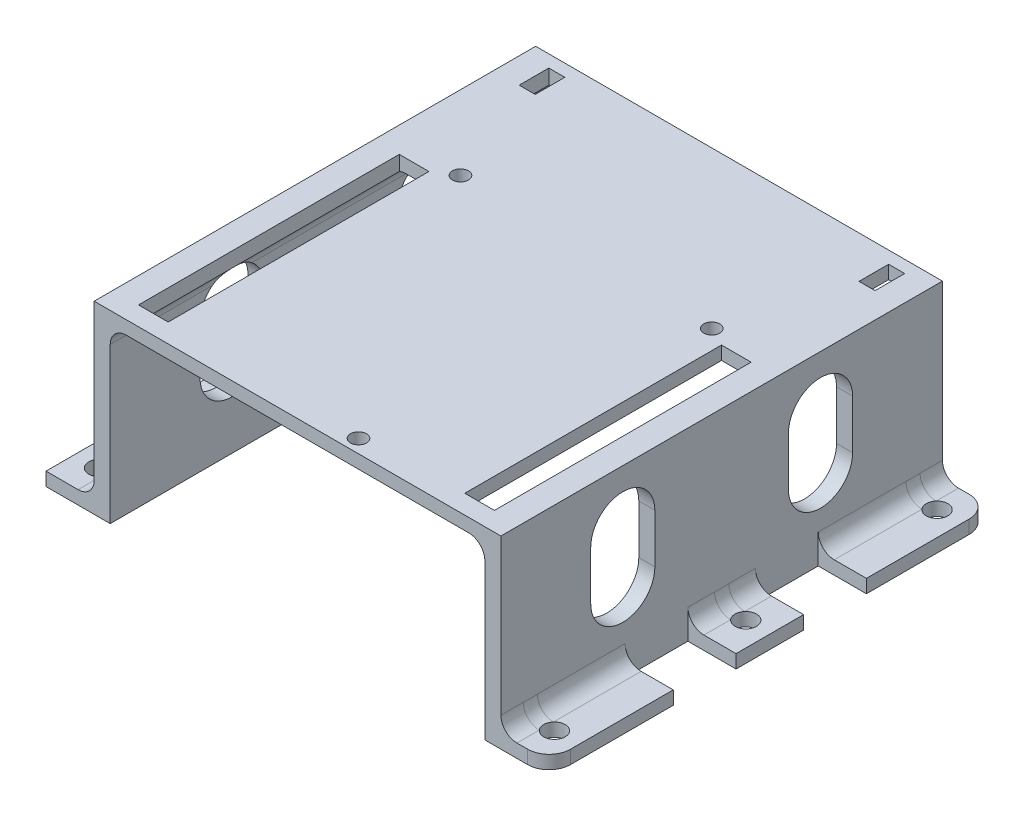
SolidWorks part; units mm, degrees
ref_plane "Front Plane" through (0, 0, 0) normal (0, 0, 1) x (1, 0, 0)
ref_plane "Top Plane" through (0, 0, 0) normal (0, 1, 0) x (1, 0, 0)
ref_plane "Right Plane" through (0, 0, 0) normal (1, 0, 0) x (0, 0, -1)
sketch "Sketch1" plane through (0, 0, 0) normal (0, 1, 0) x (1, 0, 0)
  line L0 (-35, 41.25) -> (-38, 41.25)
  line L1 (-35, -41.25) -> (35, -41.25)
  line L2 (-35, -41.25) -> (-35, 41.25)
  line L3 (-35, 41.25) -> (35, 41.25)
  line L4 (35, -41.25) -> (35, 41.25)
  line L5 (-35, -41.25) -> (35, 41.25) construction
  line L6 (-35, 41.25) -> (35, -41.25) construction
  line L7 (-38, 41.25) -> (-38, -41.25)
  line L8 (-38, -41.25) -> (-35, -41.25)
  line L9 (-38, -41.25) -> (-47, -41.25)
  line L10 (-47, -41.25) -> (-47, 41.25)
  line L11 (-47, 41.25) -> (-38, 41.25)
  line L12 (0, 21.0903) -> (0, -28.1695) construction
  line L13 (47, 41.25) -> (38, 41.25)
  line L14 (47, -41.25) -> (47, 41.25)
  line L15 (38, -41.25) -> (47, -41.25)
  line L16 (38, 41.25) -> (38, -41.25)
  line L17 (38, -41.25) -> (35, -41.25)
  line L18 (35, 41.25) -> (38, 41.25)
  line L19 (-42.5, 41.25) -> (-42.5, -41.25) construction
  line L20 (42.5, 41.25) -> (42.5, -41.25) construction
  line L21 (-58.5063, 0) -> (72.588, 0) construction
  circle A0 centre (-42.5, 35.75) radius 2
  circle A1 centre (-42.5, -35.75) radius 2
  circle A2 centre (42.5, -35.75) radius 2
  circle A3 centre (42.5, 35.75) radius 2
  circle A4 centre (-42.5, 0) radius 2
  circle A5 centre (42.5, 0) radius 2
  point P0 (0, 0)
  dimension "D3" = 4
  dimension "D4" = 4
  dimension "D5" = 5.5
  dimension "D9" = 4
  dimension "D10" = 4
  dimension "D1" = 3
  dimension "D2" = 9
  dimension "D6" = 5.5
  dimension "D7" = 82.5
  dimension "D8" = 70
extrude "Boss-Extrude1" add sketch "Sketch1" along normal blind 2.5 contours L11 L10 L9 L7 A1 A0 | L13 L16 L15 L14 A2 A3 region at (-38.8299, 0, 0) region at (42.5, 0, -40.4201)
extrude "Boss-Extrude2" add sketch "Sketch1<3>" along normal blind 32 contours L7 L8 L2 L0 | L18 L4 L17 L16 region at (-36.5, 0, 0) region at (36.5, 0, 0)
sketch "Sketch1<3>" plane through (0, 0, 0) normal (0, 1, 0) x (1, 0, 0) same geometry as "Sketch1"
extrude "Boss-Extrude3" add sketch "Sketch1<5>" along normal blind 2.5 from surface contours L7 L8 L2 L0 | L18 L4 L17 L16 | L1 L4 L3 L2 region at (-36.5, 0, 0) region at (0, 0, 0) region at (36.5, 0, 0) starting at face at (-36.5, 32, 0)
sketch "Sketch1<5>" plane through (0, 0, 0) normal (0, 1, 0) x (1, 0, 0) same geometry as "Sketch1"
fillet "Fillet1" radius 3 2 edges at (35, 32, 0) (-35, 32, 0)
fillet "Fillet2" radius 4 2 edges at (47, 1.25, 41.25) (47, 1.25, -41.25)
sketch "Sketch2" plane through (0, 2.5, 0) normal (0, 1, 0) x (1, 0, 0)
  line L0 (-42.5, 0) -> (42.5, 0) construction
  line L1 (48.0101, 18.0465) -> (38, 18.0465)
  line L2 (38, -41.25) -> (38, 41.25) construction
  line L3 (38, 18.0465) -> (38, 6.3106)
  line L4 (38, 6.3106) -> (48.0101, 6.3106)
  line L5 (48.0101, 6.3106) -> (48.0101, 18.0465)
  line L6 (48.0101, -6.3106) -> (48.0101, -18.0465)
  line L7 (38, -6.3106) -> (48.0101, -6.3106)
  line L8 (38, -18.0465) -> (38, -6.3106)
  line L9 (48.0101, -18.0465) -> (38, -18.0465)
extrude "Cut-Extrude1" cut sketch "Sketch2" against normal through all both and the other way through all
fillet "Fillet4" radius 3 4 edges at (-38, 2.5, 0) (38, 2.5, 29.6482) (38, 2.5, 0) (38, 2.5, -29.6482)
sketch "Sketch3" plane through (-38, 0, 0) normal (-1, 0, 0) x (0, 0, 1)
  line L0 (18.4733, 15.128) -> (18.4733, 24.2824) construction
  line L1 (12.4833, 15.128) -> (12.4833, 24.2824)
  line L2 (24.4633, 15.128) -> (24.4633, 24.2824)
  line L3 (0, 7.6501) -> (0, 29.8023) construction
  line L4 (-18.4733, 15.128) -> (-18.4733, 24.2824) construction
  line L5 (-12.4833, 15.128) -> (-12.4833, 24.2824)
  line L6 (-24.4633, 15.128) -> (-24.4633, 24.2824)
  arc A0 (12.4833, 15.128) -> (24.4633, 15.128) centre (18.4733, 15.128) ccw
  arc A1 (24.4633, 24.2824) -> (12.4833, 24.2824) centre (18.4733, 24.2824) ccw
  arc A2 (-12.4833, 15.128) -> (-24.4633, 15.128) centre (-18.4733, 15.128) cw
  arc A3 (-24.4633, 24.2824) -> (-12.4833, 24.2824) centre (-18.4733, 24.2824) cw
  point P2 (18.4733, 19.7052)
  point P12 (-18.4733, 19.7052)
extrude "Cut-Extrude2" cut sketch "Sketch3" against normal through all both and the other way through all
sketch "Sketch4" plane through (0, 34.5, 0) normal (0, 1, 0) x (1, 0, 0)
  line L0 (-38, -41.25) -> (-38, 41.25) construction
  line L1 (38, -41.25) -> (-38, -41.25) construction
  line L2 (-31.75, -36.21) -> (-29.21, -36.21) construction
  line L3 (-31.75, -36.21) -> (-31.75, 9.51) construction
  line L4 (-31.75, 9.51) -> (-29.21, 9.51) construction
  line L5 (-29.21, -36.21) -> (-29.21, 9.51) construction
  line L6 (29.21, -36.21) -> (31.75, -36.21) construction
  line L7 (29.21, -36.21) -> (29.21, 9.51) construction
  line L8 (29.21, 9.51) -> (31.75, 9.51) construction
  line L9 (31.75, -36.21) -> (31.75, 9.51) construction
  line L10 (-31.75, 34.91) -> (-31.75, 37.45) construction
  line L11 (-33.25, -37.71) -> (-27.71, -37.71)
  line L12 (-33.25, -37.71) -> (-33.25, 11.01)
  line L13 (-33.25, 11.01) -> (-27.71, 11.01)
  line L14 (-27.71, -37.71) -> (-27.71, 11.01)
  line L15 (27.71, -37.71) -> (33.25, -37.71)
  line L16 (27.71, -37.71) -> (27.71, 10.26)
  line L17 (27.71, 10.26) -> (33.25, 10.26)
  line L18 (33.25, -37.71) -> (33.25, 10.26)
  line L19 (31.75, 34.91) -> (31.75, 37.45) construction
  line L21 (-31.75, 37.45) -> (31.75, 37.45) construction
  line L23 (-33.25, 33.41) -> (-30.25, 33.41)
  line L24 (-33.25, 33.41) -> (-33.25, 38.95)
  line L25 (-33.25, 38.95) -> (-30.25, 38.95)
  line L26 (-30.25, 33.41) -> (-30.25, 38.95)
  line L27 (30.25, 33.41) -> (33.25, 33.41)
  line L28 (30.25, 33.41) -> (30.25, 38.95)
  line L29 (30.25, 38.95) -> (33.25, 38.95)
  line L30 (33.25, 33.41) -> (33.25, 38.95)
  circle A0 centre (-24.13, 13.32) radius 1.5
  circle A1 centre (24.13, 12.03) radius 1.5
  circle A2 centre (8.89, -38.75) radius 1.5
  point P30 (-30.48, -36.21)
  dimension "D1" = 3
  dimension "D2" = 2.54
  dimension "D3" = 3
  dimension "D4" = 3
  dimension "D5" = 46.89
  dimension "D6" = 5.04
  dimension "D7" = 2.54
  dimension "D8" = 2.54
  dimension "D9" = 45.72
  dimension "D10" = 3.81
  dimension "D11" = 7.62
  dimension "D12" = 48.26
  dimension "D13" = 63.5
  dimension "D14" = 6.25
  dimension "D15" = 48.24
  dimension "D16" = 1.5
  dimension "D17" = 1.5
  dimension "D18" = 1.5
  dimension "D19" = 1.5
  dimension "D20" = 1.5
  dimension "D21" = 1.5
  dimension "D22" = 1.5
  dimension "D23" = 1.5
  dimension "D24" = 2.54
  dimension "D25" = 71.12
  dimension "D26" = 1.5
  dimension "D27" = 1.5
  dimension "D28" = 1.5
  dimension "D29" = 1.5
  dimension "D30" = 1.5
  dimension "D31" = 1.5
  dimension "D32" = 1.5
  dimension "D33" = 1.5
extrude "Cut-Extrude3" cut sketch "Sketch4" against normal through all both and the other way through all
